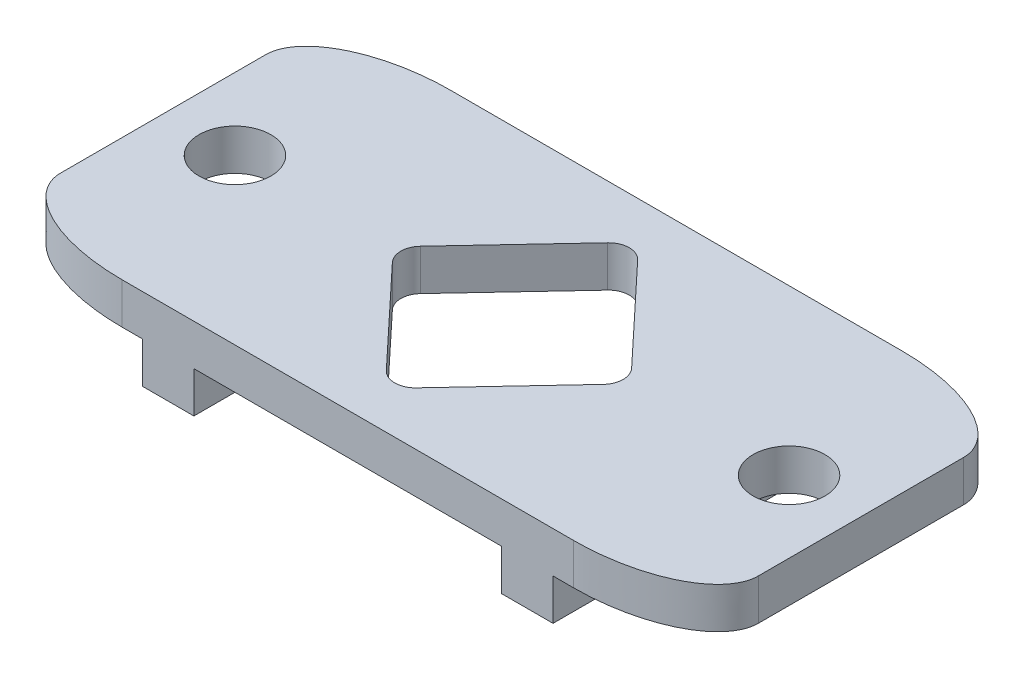
SolidWorks part; units mm, degrees
note: The reader was unsure of these and kept them because the rebuilt part matched: shared geometry of "Sketch1<3>".
ref_plane "Plan de face" through (0, 0, 0) normal (0, 0, 1) x (1, 0, 0)
ref_plane "Plan de dessus" through (0, 0, 0) normal (0, 1, 0) x (1, 0, 0)
ref_plane "Plan de droite" through (0, 0, 0) normal (1, 0, 0) x (0, 0, -1)
sketch "Sketch1" plane through (0, 0, 0) normal (0, 1, 0) x (1, 0, 0)
  line L0 (-10, 8) -> (-10, -8)
  line L1 (-17, -8) -> (17, -8)
  line L2 (-17, -8) -> (-17, 8)
  line L3 (-17, 8) -> (17, 8)
  line L4 (17, -8) -> (17, 8)
  line L5 (-17, -8) -> (17, 8) construction
  line L6 (-17, 8) -> (17, -8) construction
  line L7 (-7.5, 8) -> (-7.5, -8)
  line L8 (7.5, 8) -> (7.5, -8)
  line L9 (10, 8) -> (10, -8)
  line L10 (0, 0) -> (0, 8) construction
  circle A0 centre (-13.5, 0) radius 1.75
  circle A1 centre (13.5, 0) radius 1.75
  point P0 (0, 0)
  point P18 (-11.8015, 0)
  point P19 (0, 0)
  dimension "D5" = 3.5
  dimension "D1" = 34
  dimension "D2" = 2.5
  dimension "D3" = 2.5
  dimension "D4" = 16
  dimension "D6" = 3.5
  dimension "D7" = 7
  dimension "D8" = 15
extrude "Boss-Extrude1" add sketch "Sketch1" along normal blind 2 contours A0 | A1 | L3 L4 L1 L2
extrude "Boss-Extrude2" add sketch "Sketch1<3>" against normal blind 2 contours L7 L3 L0 L1 | L9 L3 L8 L1
sketch "Sketch1<3>" plane through (0, 0, 0) normal (0, 1, 0) x (1, 0, 0) same geometry as "Sketch1"
sketch "Sketch2" plane through (0, 0, 0) normal (0, -1, 0) x (1, 0, 0)
  line L0 (0, 8) -> (-7.5, 0) construction
  line L1 (-7.5, 0) -> (0, -8) construction
  line L2 (0, -8) -> (7.5, 0) construction
  line L3 (7.5, 0) -> (0, 8) construction
  line L4 (7.5, -8) -> (7.5, 8)
  line L5 (7.5, 8) -> (-7.5, 8)
  line L6 (-7.5, 8) -> (-7.5, -8)
  line L7 (-7.5, -8) -> (7.5, -8)
  line L8 (7.5, -8) -> (7.5, 8)
  line L9 (7.5, 8) -> (-7.5, 8)
  line L10 (-7.5, 8) -> (-7.5, -8)
  line L11 (-7.5, -8) -> (7.5, -8)
  line L12 (5.1454, 0.6839) -> (0.7295, 5.3942)
  line L13 (-0.7295, 5.3942) -> (-5.1454, 0.6839)
  line L14 (-5.1454, -0.6839) -> (-0.7295, -5.3942)
  line L15 (0.7295, -5.3942) -> (5.1454, -0.6839)
  line L16 (0, 6.1724) -> (-5.7866, 0) construction
  line L17 (5.7866, 0) -> (0, 6.1724) construction
  line L18 (0, -6.1724) -> (5.7866, 0) construction
  line L19 (-5.7866, 0) -> (0, -6.1724) construction
  arc A0 (-0.7295, 5.3942) -> (0.7295, 5.3942) centre (0, 4.7102) cw
  arc A1 (5.1454, 0.6839) -> (5.1454, -0.6839) centre (4.4159, 0) cw
  arc A2 (-0.7295, -5.3942) -> (0.7295, -5.3942) centre (0, -4.7102) ccw
  arc A3 (-5.1454, -0.6839) -> (-5.1454, 0.6839) centre (-4.4159, 0) cw
  dimension "D3" = 1
  dimension "D1" = 0
  dimension "D2" = 1.25
extrude "Cut-Extrude2" cut sketch "Sketch2" against normal through all contours A3 L14 A2 L15 A1 L12 A0 L13
fillet "Fillet1" radius 6 2 edges at (17, 1, 8) (-17, 1, -8)
fillet "Fillet2" radius 6 2 edges at (17, 1, -8) (-17, 1, 8)
